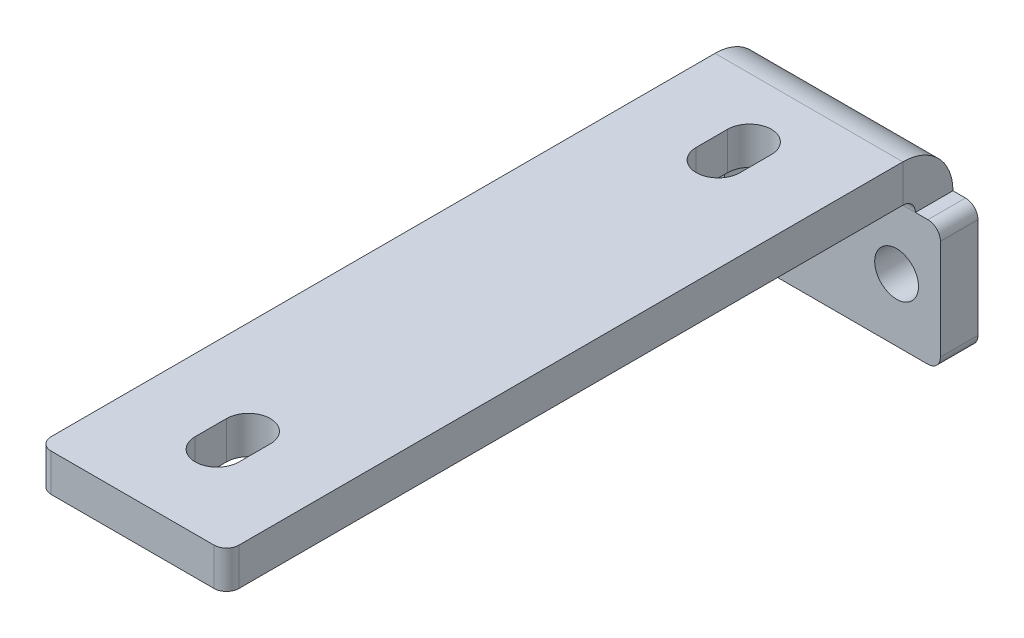
SolidWorks part; units mm, degrees
note: The reader was unsure of these and kept them because the rebuilt part matched: thickness of "Brida base1", "Brida de arista1", "Chapa metálica4", "Chapa metálica5", "Chapa metálica6"; flange length of "Brida de arista1".
material "acero"
ref_plane "Alzado" through (0, 0, 0) normal (0, 0, 1) x (1, 0, 0)
ref_plane "Planta" through (0, 0, 0) normal (0, 1, 0) x (1, 0, 0)
ref_plane "Vista lateral" through (0, 0, 0) normal (1, 0, 0) x (0, 0, -1)
sketch "Croquis1" plane through (0, 0, 0) normal (0, 0, 1) x (1, 0, 0)
  line L0 (0, -5) -> (9.5, -5) construction
  line L1 (0, 0) -> (19, 0)
  line L2 (0, 0) -> (0, -10)
  line L3 (0, -10) -> (19, -10)
  line L4 (19, 0) -> (19, -10)
  line L5 (9.5, 0) -> (9.5, -10) construction
  circle A0 centre (3.5, -5) radius 1.75
  circle A1 centre (15.5, -5) radius 1.75
  dimension "D1" = 3.5
  dimension "D2" = 3.5
  dimension "D3" = 12
  dimension "D4" = 5
base flange "Brida base1" sketch "Croquis1" thickness 3 reverse thickness direction no parameters "D1"=1
edge flange "Brida de arista1" sketch "Croquis8" flange angle 90 flange length 55 flange position bend outside bend radius 1 thickness 3 relief rectangular parameters "D6"=10
sketch "Croquis8" plane through (0, 0, 0) normal (0, 1, 0) x (-1, 0, 0)
  line L3 (-17, 55) -> (-2, 55)
  line L4 (-2, 0) -> (-2, 55)
  line L5 (-19, 0) -> (0, 0) construction
  line L6 (-9.5, 0) -> (-9.5, 39.9038) construction
  line L7 (-17, 0) -> (-2, 0)
  line L9 (-17, 0) -> (-17, 55)
  line L10 (-17, 0) -> (-9.5, 0) construction
  line L11 (-9.5, 0) -> (-2, 0) construction
  dimension "D1" = 15
  dimension "D2" = 55
bend "Pliegue de arista1" bend radius 1 bend angle 90 parameters "D5"=1
sketch "Croquis9" plane through (0, 4, 0) normal (0, 1, 0) x (1, 0, 0)
  line L0 (9.5, -8.25) -> (9.5, -5.75) construction
  line L1 (7.75, -8.25) -> (7.75, -5.75)
  line L2 (11.25, -8.25) -> (11.25, -5.75)
  line L3 (9.5, -28.25) -> (9.5, -25.75) construction
  line L4 (7.75, -28.25) -> (7.75, -25.75) construction
  line L5 (17, -1) -> (2, -1) construction
  line L6 (11.25, -28.25) -> (11.25, -25.75) construction
  line L7 (9.5, -48.25) -> (9.5, -45.75) construction
  line L8 (7.75, -48.25) -> (7.75, -45.75)
  line L9 (9.5, -1) -> (9.5, -5.75) construction
  line L10 (11.25, -48.25) -> (11.25, -45.75)
  arc A0 (7.75, -28.25) -> (11.25, -28.25) centre (9.5, -28.25) ccw construction
  arc A1 (11.25, -25.75) -> (7.75, -25.75) centre (9.5, -25.75) ccw construction
  arc A2 (7.75, -8.25) -> (11.25, -8.25) centre (9.5, -8.25) ccw
  arc A3 (11.25, -5.75) -> (7.75, -5.75) centre (9.5, -5.75) ccw
  arc A4 (7.75, -48.25) -> (11.25, -48.25) centre (9.5, -48.25) ccw
  arc A5 (11.25, -45.75) -> (7.75, -45.75) centre (9.5, -45.75) ccw
  point P6 (9.5, -27)
  point P10 (9.5, -7)
  point P22 (9.5, -47)
  dimension "D1" = 6
  dimension "D3" = 40
  dimension "D5" = 1.75
  dimension "D2" = 3
  dimension "D4" = 2.5
extrude "Cortar-Extruir1" cut sketch "Croquis9" against normal up to next normal cut yes
fillet "Redondeo1" radius 1 6 edges at (19, -10, -1.5) (0, -10, -1.5) (19, 0, -1.5) (0, 0, -1.5) (17, 2.5, 55) (2, 2.5, 55)
sketch "Líneas de pliegue1" [suppressed] plane through (0, 0, 0) normal (0, 1, 0) x (1, 0, 0)
sketch "Cuadro delimitador1" [suppressed] plane through (0, 0, 0) normal (0, 1, 0) x (1, 0, 0)
sheet metal parameters "Chapa metálica4" thickness 3 parameters "D1"=1
flat pattern "Chapa desplegada4" [suppressed]
sketch "Líneas de pliegue2" plane through (0, 0, 0) normal (0, 1, 0) x (1, 0, 0)
sketch "Cuadro delimitador2" [suppressed] plane through (0, 0, 0) normal (0, 1, 0) x (1, 0, 0)
sheet metal parameters "Chapa metálica5" thickness 3 parameters "D1"=1, "D7"=2
flat pattern "Chapa desplegada4" [suppressed]
sketch "Líneas de pliegue2" plane through (0, 0, 0) normal (0, 1, 0) x (1, 0, 0)
sketch "Cuadro delimitador2" [suppressed] plane through (0, 0, 0) normal (0, 1, 0) x (1, 0, 0)
bend of the flat pattern "Aplanar-<Pliegue de arista1>1"
sheet metal parameters "Chapa metálica6" thickness 3 parameters "D1"=1, "D7"=2
flat pattern "Chapa desplegada4"
sketch "Líneas de pliegue2" plane through (0, 0, 0) normal (0, 0, 1) x (1, 0, 0)
  line L0 (25.7875, 1.9635) -> (0.2125, 1.9635) construction
  line L1 (25.7875, 1.9635) -> (0.2125, 1.9635) construction
sketch3d "Cuadro delimitador2" [suppressed]
  line L0 (26, -10, 0) -> (26, 55.627, 0) construction
  line L1 (0, -10, 0) -> (0, 55.627, 0) construction
  line L2 (26, -10, 0) -> (0, -10, 0) construction
  line L3 (26, 55.627, 0) -> (0, 55.627, 0) construction
bend of the flat pattern "Aplanar-<Pliegue de arista1>1"
